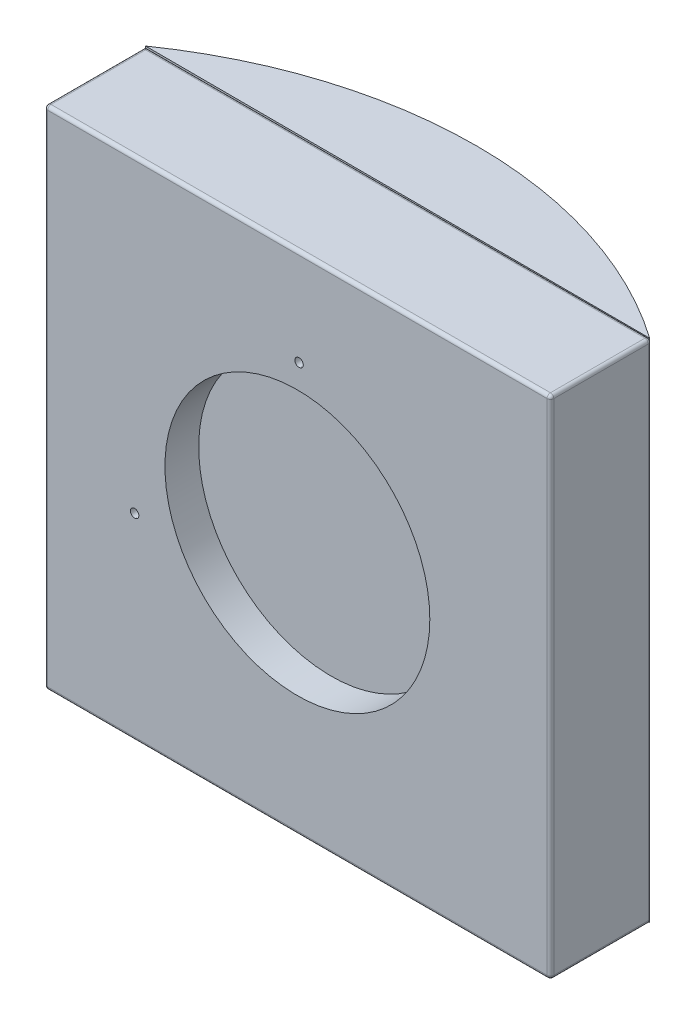
SolidWorks part; units mm, degrees
material "PLA"
ref_plane "Front Plane" through (0, 0, 0) normal (0, 0, 1) x (1, 0, 0)
ref_plane "Top Plane" through (0, 0, 0) normal (0, 1, 0) x (1, 0, 0)
ref_plane "Right Plane" through (0, 0, 0) normal (1, 0, 0) x (0, 0, -1)
sketch "Sketch1" plane through (0, 0, 0) normal (0, 0, 1) x (1, 0, 0)
  line L1 (-75, -75) -> (75, -75)
  line L2 (-75, -75) -> (-75, 75)
  line L3 (-75, 75) -> (75, 75)
  line L4 (75, -75) -> (75, 75)
  line L5 (-75, -75) -> (75, 75) construction
  line L6 (-75, 75) -> (75, -75) construction
  point P0 (0, 0)
  dimension "D1" = 150
  dimension "D2" = 150
extrude "Boss-Extrude1" add sketch "Sketch1" against normal blind 30 contours L2 L3 L4 L1
sketch "Sketch2" plane through (0, 0, 0) normal (0, 0, 1) x (1, 0, 0)
  circle A0 centre (0, 0) radius 39.25
  dimension "D1" = 78.5
fillet "Fillet1" radius 1 10 edges at (75, -75, -15) (-75, -75, -15) (-75, 75, -15) (75, 0, -30) (0, 75, -30) (75, 75, -15) (0, -75, 0) (-75, 0, 0) (75, 0, 0) (0, 75, 0)
sketch "Sketch7" plane through (0, 0, 0) normal (0, 1, 0) x (1, 0, 0)
  line L1 (-39.7685, 40.3246) -> (-29.7685, 40.3246)
  line L2 (-39.7685, 40.3246) -> (-39.7685, 30.3246)
  line L3 (-39.7685, 30.3246) -> (-29.7685, 30.3246)
  line L4 (-29.7685, 40.3246) -> (-29.7685, 30.3246)
  dimension "D1" = 10
  dimension "D2" = 10
ref_axis "Axis2" through (0, 0, 0) along (0, 0, -1)
extrude "Cut-Extrude4" cut sketch "Sketch2" against normal blind 10 contours A0
hole_wizard "Tap Drill for M6x1.0 Tap1" positions "Sketch9" profile "Sketch10" hole size "M6x1.0" standard "ANSI Metric"
sketch "Sketch9" plane through (0, 0, -30) normal (0, 0, -1) x (-1, 0, 0)
  point P0 (-61.5285, 5.5888)
  point P3 (-61.4369, -13.8864)
  point P6 (66.9905, 6.1936)
  point P9 (67.0821, -13.2817)
sketch "Sketch10" plane through (61.5285, 5.5888, -30) normal (1, 0, 0) x (0, 1, 0)
  line L0 (0, 0) -> (0, 13.5022)
  line L1 (0, 13.5022) -> (2.5, 12)
  line L2 (2.5, 12) -> (2.5, 0)
  line L5 (2.5, 0) -> (0, 0)
  line L10 (0, 13.5022) -> (-2.5, 12) construction
  line L11 (0, -6.35) -> (0, 107.95) construction
  dimension "Hole Dia." = 5
  dimension "Hole Depth" = 12
  dimension "Drill Angle" = 118
sketch "Sketch11" plane through (0, -75, 0) normal (0, -1, 0) x (1, 0, 0)
  line L0 (-75, -30) -> (74.7071, -29.7071)
  arc A0 (74, -30) -> (75, -29) centre (74, -29) ccw construction
  arc A1 (-75, -30) -> (74.7071, -29.7071) centre (-0.3559, 77.2092) ccw
extrude "Boss-Extrude2" add sketch "Sketch11" against normal up to surface (150 mm away) up to face at (0, 75, -15)
sketch "Sketch18" plane through (0, 0, 0) normal (0, 0, 1) x (1, 0, 0)
  circle A0 centre (0.4962, 46.5) radius 2.475
  circle A1 centre (-48.2375, -16.5473) radius 2.475
hole_wizard "Tap Drill for M3x0.5 Tap3" positions "Sketch19" profile "Sketch20" hole size "M3x0.5" standard "ANSI Metric"
sketch "Sketch19" plane through (0, 0, 0) normal (0, 0, 1) x (1, 0, 0)
  point P0 (0.4962, 46.5)
  point P3 (-48.2375, -16.5473)
sketch "Sketch20" plane through (0.4962, 46.5, 0) normal (1, 0, 0) x (0, -1, 0)
  line L0 (0, 0) -> (0, 10.7511)
  line L1 (0, 10.7511) -> (1.25, 10)
  line L2 (1.25, 10) -> (1.25, 0)
  line L5 (1.25, 0) -> (0, 0)
  line L10 (0, 10.7511) -> (-1.25, 10) construction
  line L11 (0, -6.35) -> (0, 107.95) construction
  dimension "Hole Dia." = 2.5
  dimension "Hole Depth" = 10
  dimension "Drill Angle" = 118
